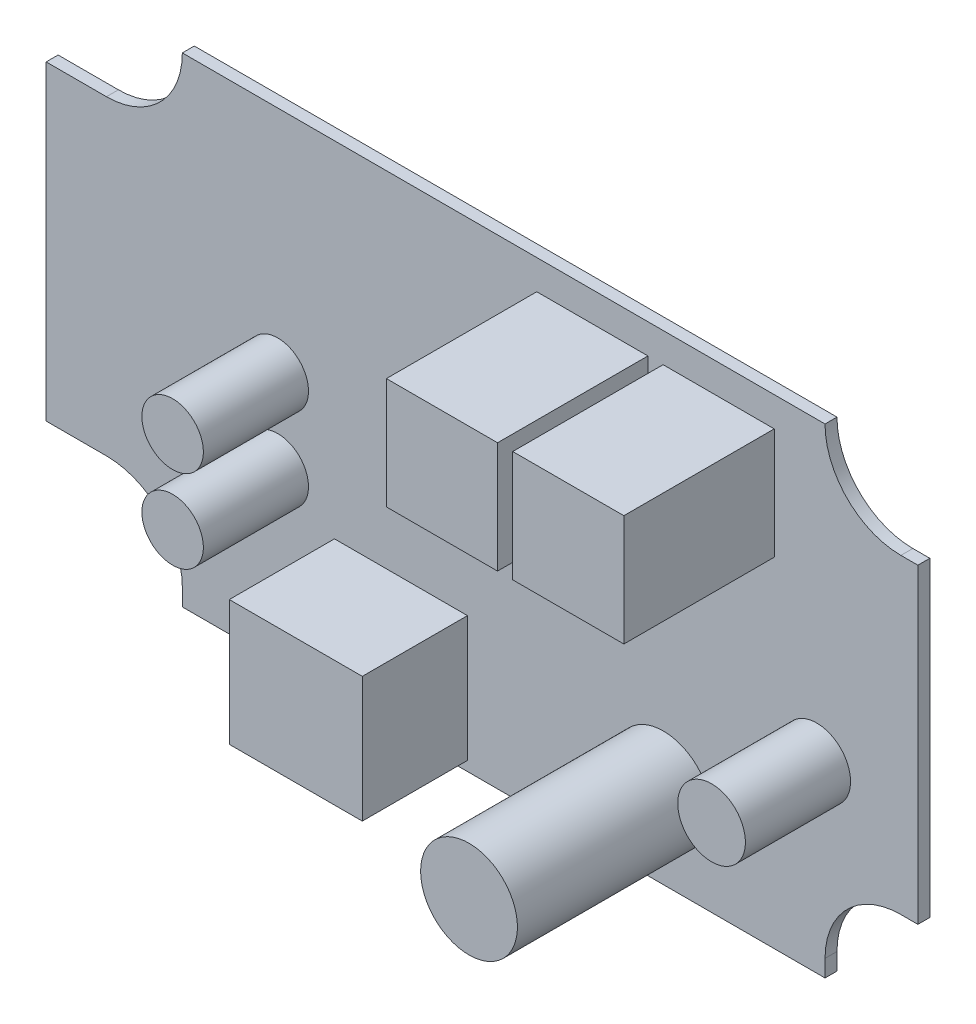
SolidWorks part; units mm, degrees
ref_plane "Front Plane" through (0, 0, 0) normal (0, 0, 1) x (1, 0, 0)
ref_plane "Top Plane" through (0, 0, 0) normal (0, 1, 0) x (1, 0, 0)
ref_plane "Right Plane" through (0, 0, 0) normal (1, 0, 0) x (0, 0, -1)
sketch "Sketch1" plane through (0, 0, 0) normal (0, 0, 1) x (1, 0, 0)
  line L0 (-42.3541, 30.2967) -> (-52.3541, 30.2967) construction
  line L1 (42.3541, -30.7033) -> (42.3541, -32.9433)
  line L2 (-52.3541, -20.7033) -> (-60.3013, -20.7033)
  line L3 (-42.3541, 30.2967) -> (42.3541, 30.2967)
  line L4 (52.3541, -20.7033) -> (54.5933, -20.7033)
  line L5 (-52.3541, 30.2967) -> (-52.3541, 20.2967) construction
  line L6 (-52.3541, -20.7033) -> (-52.3541, -30.7033) construction
  line L7 (-52.3541, -30.7033) -> (-42.3541, -30.7033) construction
  line L8 (42.3541, -30.7033) -> (52.3541, -30.7033) construction
  line L9 (52.3541, -30.7033) -> (52.3541, -20.7033) construction
  line L10 (52.3541, 20.2967) -> (52.3541, 30.2967) construction
  line L11 (52.3541, 30.2967) -> (42.3541, 30.2967) construction
  line L12 (54.5933, -20.7033) -> (54.5933, 20.2967)
  line L13 (-60.3013, -20.7033) -> (-60.3013, 20.2967)
  line L14 (-60.3013, 20.2967) -> (-52.3541, 20.2967)
  line L15 (54.5933, 20.2967) -> (52.3541, 20.2967)
  line L16 (42.3541, -32.9433) -> (-42.3541, -32.9433)
  line L17 (-42.3541, -32.9433) -> (-42.3541, -30.7033)
  line L21 (0, -32.9433) -> (0, 0) construction
  arc A0 (-42.3541, 30.2967) -> (-52.3541, 20.2967) centre (-52.3541, 30.2967) cw
  arc A2 (-52.3541, -20.7033) -> (-42.3541, -30.7033) centre (-52.3541, -30.7033) cw
  arc A4 (42.3541, 30.2967) -> (52.3541, 20.2967) centre (52.3541, 30.2967) ccw
  arc A5 (52.3541, -20.7033) -> (42.3541, -30.7033) centre (52.3541, -30.7033) ccw
  dimension "D1" = 41
  dimension "D3" = 10
  dimension "D6" = 2.24
  dimension "D8" = 2.2392
extrude "Boss-Extrude1" add sketch "Sketch1" along normal blind 1.5748
sketch "Sketch2" plane through (0, 0, 1.5748) normal (0, 0, 1) x (1, 0, 0)
  line L1 (4.3619, 26.3914) -> (19.0119, 26.3914)
  line L2 (4.3619, 26.3914) -> (4.3619, 11.7414)
  line L3 (4.3619, 11.7414) -> (19.0119, 11.7414)
  line L4 (19.0119, 26.3914) -> (19.0119, 11.7414)
  line L5 (21.0119, 26.3914) -> (35.6619, 26.3914)
  line L6 (21.0119, 26.3914) -> (21.0119, 11.7414)
  line L7 (21.0119, 11.7414) -> (35.6619, 11.7414)
  line L8 (35.6619, 26.3914) -> (35.6619, 11.7414)
  dimension "D1" = 2
  dimension "D2" = 14.65
extrude "Boss-Extrude2" add sketch "Sketch2" along normal blind 19.82
sketch "Sketch3" plane through (0, 0, 1.5748) normal (0, 0, 1) x (1, 0, 0)
  circle A0 centre (21.0509, -21.7791) radius 6.38
  dimension "D1" = 12.76
extrude "Boss-Extrude3" add sketch "Sketch3" along normal blind 25.62
sketch "Sketch4" plane through (0, 0, 1.5748) normal (0, 0, 1) x (1, 0, 0)
  line L1 (-22.3027, -15.1438) -> (-4.7739, -15.1438)
  line L2 (-22.3027, -15.1438) -> (-22.3027, -31.671)
  line L3 (-22.3027, -31.671) -> (-4.7739, -31.671)
  line L4 (-4.7739, -15.1438) -> (-4.7739, -31.671)
  circle A0 centre (-29.7754, 0) radius 4.05
  circle A1 centre (-29.7754, -10.91) radius 4.05
  circle A2 centre (41.2613, -8.8411) radius 4.4585
  dimension "D1" = 8.1
  dimension "D2" = 16.5272
  dimension "D4" = 8.9169
  dimension "D3" = 17.5288
extrude "Boss-Extrude4" add sketch "Sketch4" along normal blind 13.86
